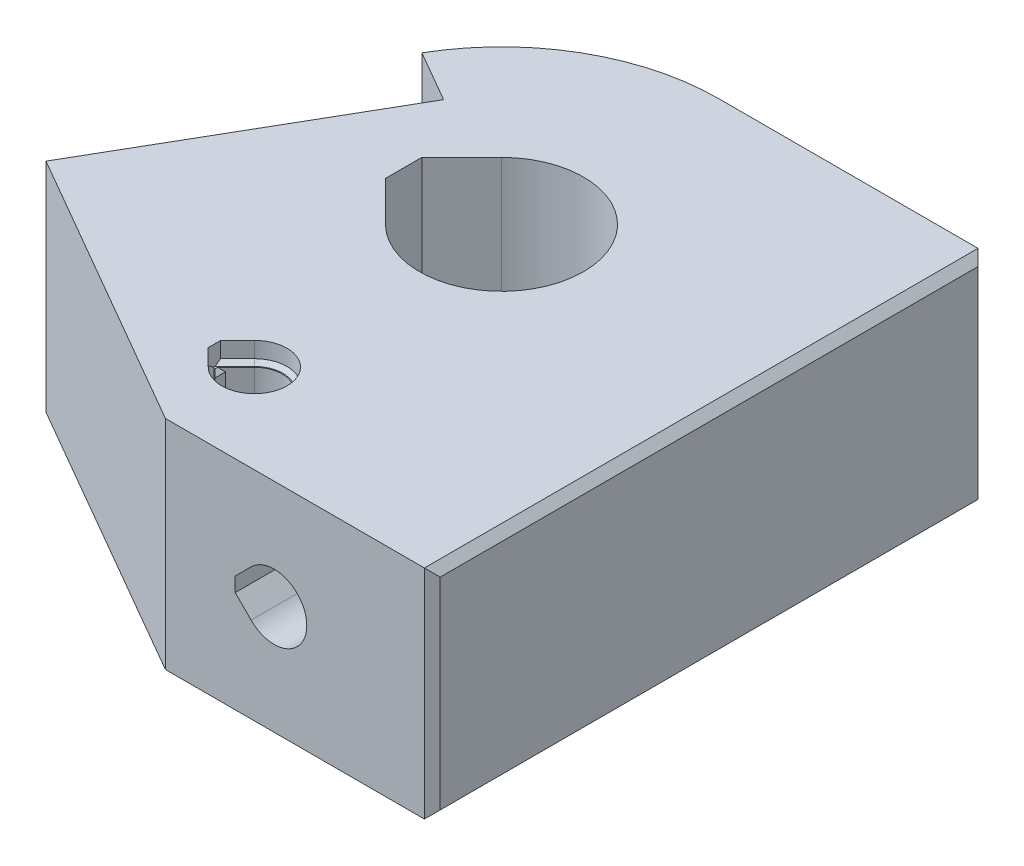
SolidWorks part; units mm, degrees
material "Custom Plastic"
ref_plane "Front Plane" through (0, 0, 0) normal (0, 0, 1) x (1, 0, 0)
ref_plane "Top Plane" through (0, 0, 0) normal (0, 1, 0) x (1, 0, 0)
ref_plane "Right Plane" through (0, 0, 0) normal (1, 0, 0) x (0, 0, -1)
sketch "Sketch1" plane through (0, 0, 0) normal (0, 1, 0) x (1, 0, 0)
  line L0 (-7.5, -1) -> (-21, -1)
  line L1 (-35.2894, 7.25) -> (-40.4856, 10.25) construction
  line L2 (-21, 24) -> (-6, 24) construction
  line L3 (0, 24) -> (0, 0) construction
  line L4 (-40.4856, 10.25) -> (-37.1244, 16.0718) construction
  line L5 (-22.7129, 20.1561) -> (-19.2871, 20.1561) construction
  line L6 (-21, 27) -> (-7.5, 27)
  line L7 (-7.5, -1) -> (-7.5, 27)
  line L8 (-35.2894, 7.25) -> (-21, -1)
  line L9 (-37.1244, 16.0718) -> (-31.9282, 13.0718) construction
  line L10 (-7.5, 11.5) -> (7.5, 20.5) construction
  line L11 (-7.5, 20.5) -> (7.5, 11.5) construction
  line L12 (-19.2871, 20.1561) -> (-18.0655, 18.9345) construction
  line L13 (-18.0655, 18.9345) -> (-21, 16) construction
  line L14 (-21, 16) -> (-23.9345, 18.9345) construction
  line L15 (-23.9345, 18.9345) -> (-22.7129, 20.1561) construction
  line L16 (-27.9282, 20) -> (-31.9282, 13.0718)
  line L17 (-27.9282, 20) -> (-30.5263, 21.5)
  line L18 (-31.9282, 13.0718) -> (-35.2894, 7.25)
  arc A0 (-21, 24) -> (-27.5362, 11.3872) centre (-21, 16) ccw construction
  circle A1 centre (-21, 16) radius 4.15
  arc A2 (-21, 27) -> (-30.5263, 21.5) centre (-21, 16) ccw
  point P10 (0, 16)
  point P22 (-21, 20.1561)
  dimension "D4" = 8.3
  dimension "D5" = 8
  dimension "D9" = 3
  dimension "D2" = 42
  dimension "D3" = 25
  dimension "D6" = 9
  dimension "D7" = 15
  dimension "D8" = 16
  dimension "D10" = 30
  dimension "D11" = 42
  dimension "D12" = 6
  dimension "D13" = 8
extrude "Boss-Extrude1" add sketch "Sketch1" along normal blind 11
sketch "Sketch2" plane through (0, 0, 1) normal (0, 0, 1) x (1, 0, 0)
  line L0 (-22.5, 21) -> (0, 21) construction
  line L1 (-15.5, 36.5) -> (15.5, 36.5) construction
  line L2 (-15.5, 36.5) -> (-15.5, 5.5) construction
  line L3 (-15.5, 5.5) -> (15.5, 5.5) construction
  line L4 (15.5, 36.5) -> (15.5, 5.5) construction
  line L5 (-15.5, 36.5) -> (15.5, 5.5) construction
  line L6 (-15.5, 5.5) -> (15.5, 36.5) construction
  line L9 (-21, 0) -> (-7.5, 0) construction
  circle A0 centre (-15.5, 36.5) radius 1.65 construction
  circle A1 centre (15.5, 36.5) radius 1.65 construction
  circle A2 centre (15.5, 5.5) radius 1.65 construction
  circle A4 centre (0, 21) radius 11.2 construction
  circle A5 centre (-15.5, 5.5) radius 1.65
  point P0 (0, 21)
  dimension "D2" = 3.3
  dimension "D3" = 22.4
  dimension "D1" = 31
  dimension "D4" = 21
extrude "Cut-Extrude1" cut sketch "Sketch2" against normal through all
sketch "Sketch3" plane through (0, 0, -27) normal (0, 0, -1) x (-1, 0, 0)
  circle A1 centre (15.5, 5.5) radius 3.7
  circle A2 centre (15.5, 5.5) radius 1.65 construction
  dimension "D1" = 7.4
extrude "Cut-Extrude2" cut sketch "Sketch3" against normal blind 11
sketch "Sketch5" plane through (0, 11, 0) normal (0, 1, 0) x (1, 0, 0)
  line L0 (0, 0) -> (0, 3.5) construction
  line L1 (-21, 3.5) -> (21, 3.5) construction
  line L3 (-21, 3.5) -> (-20.3764, 4.7535) construction
  line L4 (-20.3764, 4.7535) -> (-23.4917, 6.3032) construction
  line L5 (-21, 3.5) -> (-22.5871, 4.2896) construction
  line L6 (-22.5871, 4.2896) -> (-18.5083, 6.3032) construction
  line L7 (-18.5083, 6.3032) -> (-23.4917, 6.3032) construction
  circle A0 centre (-21, 3.5) radius 1.4
  circle A1 centre (-21, 16) radius 4.15 construction
  point P10 (-21, 6.3032)
  dimension "D1" = 2.8
  dimension "D2" = 42
  dimension "D3" = 12.5
extrude "Cut-Extrude4" cut sketch "Sketch5" against normal through all
ref_axis "Axis1" [suppressed] through (0, 6, -27) along (0, 0, 1)
ref_plane "Plane1" [suppressed] through (0, 6, 0) normal (0, 1, 0) x (1, 0, 0)
ref_axis "Axis2" through (-21, 0, -3.5) along (0, 1, 0)
ref_plane "Plane2" through (0, 5.5, 0) normal (0, 1, 0) x (1, 0, 0)
sketch "Sketch11" plane through (-29.6064, 0, -17.0933) normal (-0.866, 0, -0.5) x (-0.5, 0, 0.866)
  line L0 (15.2842, 5.5) -> (-15.2842, 5.5) construction
  line L1 (-3.3564, 11) -> (-3.3564, 0) construction
  circle A0 centre (3.6436, 5.5) radius 1.4
  dimension "D2" = 2.8
  dimension "D1" = 7
extrude "Cut-Extrude10" cut sketch "Sketch11" against normal blind 14
sketch "Sketch10" [suppressed] plane through (-29.6064, 0, -17.0933) normal (-0.866, 0, -0.5) x (-0.5, 0, 0.866)
  line L0 (0.8936, 11) -> (6.3936, 11)
  line L1 (3.6436, 2.1246) -> (6.3936, 3.7123)
  line L2 (6.3936, 3.7123) -> (6.3936, 11)
  line L3 (6.9561, 6.563) -> (3.6436, 8.4754) construction
  line L4 (3.6436, 8.4754) -> (1.4561, 7.2125) construction
  line L5 (0.8936, 11) -> (0.8936, 3.7123)
  line L6 (0.8936, 3.7123) -> (3.6436, 2.1246)
  line L7 (-3.3564, 11) -> (11.366, 11) construction
  circle A0 centre (3.6436, 5.3) radius 2.75 construction
  point P1 (3.6436, 5.5)
  dimension "D2" = 5.5
  dimension "D1" = 0.2
extrude "Cut-Extrude9" [suppressed] cut sketch "Sketch10" against normal blind 4 from offset 9 offset against normal yes
sketch "Sketch13" plane through (0, 0, -27) normal (0, 0, -1) x (-1, 0, 0)
  line L0 (15.5, 5.5) -> (18.1163, 8.1163)
  line L1 (18.1163, 8.1163) -> (19.94, 6.2926)
  line L2 (19.94, 6.2926) -> (19.94, 4.7074)
  line L3 (19.94, 4.7074) -> (18.1163, 2.8837)
  line L4 (18.1163, 2.8837) -> (15.5, 5.5)
  line L5 (15.2842, 5.5) -> (-15.2842, 5.5) construction
  circle A0 centre (15.5, 5.5) radius 3.7 construction
  arc A2 (16.85, 2.0551) -> (16.85, 8.9449) centre (15.5, 5.5) ccw construction
  point P7 (19.94, 5.5)
  point P9 (19.2, 5.5)
  dimension "D1" = 0.74
extrude "Cut-Extrude12" [suppressed] cut sketch "Sketch13" against normal up to surface (11 mm away)
sketch "Sketch14" plane through (0, 0, 1) normal (0, 0, 1) x (1, 0, 0)
  line L0 (-15.5, 5.5) -> (-16.6667, 6.6667)
  line L1 (-16.6667, 6.6667) -> (-17.47, 5.8635)
  line L2 (-17.47, 5.8635) -> (-17.47, 5.1365)
  line L3 (-17.47, 5.1365) -> (-16.6667, 4.3333)
  line L4 (-16.6667, 4.3333) -> (-15.5, 5.5)
  line L5 (15.2842, 5.5) -> (-15.2842, 5.5) construction
  circle A0 centre (-15.5, 5.5) radius 1.65 construction
  point P9 (-17.15, 5.5)
  dimension "D1" = 0.32
extrude "Cut-Extrude13" [suppressed] cut sketch "Sketch14" against normal through all
sketch "Sketch16" plane through (0, 0, 0) normal (0, -1, 0) x (1, 0, 0)
  line L0 (-21, -16) -> (-23.9345, -18.9345)
  line L1 (-23.9345, -18.9345) -> (-25.95, -16.919)
  line L2 (-25.95, -16.919) -> (-25.95, -15.081)
  line L3 (-25.95, -15.081) -> (-23.9345, -13.0655)
  line L4 (-23.9345, -13.0655) -> (-21, -16)
  circle A0 centre (-21, -16) radius 4.15 construction
  point P7 (-25.15, -16)
  dimension "D1" = 0.8
extrude "Cut-Extrude14" cut sketch "Sketch16" against normal through all
chamfer "Chamfer1" [suppressed] distance 0.4 angle 45
sketch "Sketch17" plane through (0, 0, -27) normal (0, 0, -1) x (-1, 0, 0)
  line L0 (15.5, 5.5) -> (18.1163, 2.8837)
  line L1 (18.1163, 2.8837) -> (19.94, 4.7074)
  line L2 (19.94, 4.7074) -> (19.94, 6.2926)
  line L3 (19.94, 6.2926) -> (18.1163, 8.1163)
  line L4 (18.1163, 8.1163) -> (15.5, 5.5)
  line L5 (15.5, 5.5) -> (19.94, 5.5) construction
  arc A0 (16.85, 8.9449) -> (16.85, 2.0551) centre (15.5, 5.5) ccw construction
  circle A1 centre (15.5, 5.5) radius 3.7 construction
  arc A2 (16.85, 2.0551) -> (16.85, 8.9449) centre (15.5, 5.5) ccw construction
  point P6 (19.2, 5.5)
  dimension "D1" = 0.74
extrude "Cut-Extrude15" cut sketch "Sketch17" against normal up to surface (11 mm away) up to face at (-14.8375, 5.5, -16)
sketch "Sketch18" plane through (0, 0, 1) normal (0, 0, 1) x (1, 0, 0)
  line L0 (-15.5, 5.5) -> (-16.6667, 6.6667)
  line L1 (-16.6667, 6.6667) -> (-17.47, 5.8635)
  line L2 (-17.47, 5.8635) -> (-17.47, 5.1365)
  line L3 (-17.47, 5.1365) -> (-16.6667, 4.3333)
  line L4 (-16.6667, 4.3333) -> (-15.5, 5.5)
  line L5 (-15.5, 5.5) -> (-17.47, 5.5) construction
  circle A0 centre (-15.5, 5.5) radius 1.65 construction
  point P9 (-17.15, 5.5)
  dimension "D1" = 0.32
extrude "Cut-Extrude16" cut sketch "Sketch18" against normal through all
sketch "Sketch19" [suppressed] plane through (-29.6064, 0, -17.0933) normal (-0.866, 0, -0.5) x (-0.5, 0, 0.866)
  line L0 (3.6436, 5.5) -> (4.6335, 6.4899)
  line L1 (4.6335, 6.4899) -> (4.0694, 7.0541)
  line L2 (4.0694, 7.0541) -> (3.2178, 7.0541)
  line L3 (3.2178, 7.0541) -> (2.6536, 6.4899)
  line L4 (2.6536, 6.4899) -> (3.6436, 5.5)
  circle A0 centre (3.6436, 5.5) radius 1.4 construction
  circle A1 centre (3.6436, 5.5) radius 1.4 construction
  point P6 (4.3047, 6.7341)
  dimension "D1" = 0.32
extrude "Cut-Extrude17" [suppressed] cut sketch "Sketch19" against normal up to surface (14 mm away)
sketch "Sketch23" plane through (0, 0, 0) normal (0, -1, 0) x (1, 0, 0)
  line L0 (-21.9899, -2.5101) -> (-22.72, -3.2401)
  line L1 (-22.72, -3.2401) -> (-22.72, -3.7599)
  line L2 (-22.72, -3.7599) -> (-21.9899, -4.4899)
  line L3 (-21.9899, -4.4899) -> (-21.9899, -2.5101)
  line L4 (-21, -3.5) -> (-22.72, -3.5) construction
  circle A0 centre (-21, -3.5) radius 1.4 construction
  point P9 (-22.4, -3.5)
  dimension "D1" = 0.32
extrude "Cut-Extrude21" cut sketch "Sketch23" against normal through all
sketch "Sketch20" plane through (0, 11, 0) normal (0, 1, 0) x (1, 0, 0)
  circle A0 centre (-21, 3.5) radius 1.65
  dimension "D1" = 3.3
extrude "Cut-Extrude18" cut sketch "Sketch20" against normal blind 1
sketch "Sketch21" plane through (0, 0, 0) normal (0, -1, 0) x (1, 0, 0)
  circle A0 centre (-21, -3.5) radius 1.65
  circle A1 centre (-21, -3.5) radius 1.65 construction
extrude "Cut-Extrude19" cut sketch "Sketch21" against normal blind 1
sketch "Sketch24" plane through (0, 0, 0) normal (0, -1, 0) x (1, 0, 0)
  line L0 (-22.1667, -2.3333) -> (-23.02, -3.1865)
  line L1 (-23.02, -3.1865) -> (-23.02, -3.8135)
  line L2 (-23.02, -3.8135) -> (-22.1667, -4.6667)
  line L3 (-22.1667, -4.6667) -> (-22.1667, -2.3333)
  line L4 (-22.6074, -3.1275) -> (-21.9899, -2.5101) construction
  line L5 (-22.72, -3.2401) -> (-22.72, -3.7599) construction
  arc A0 (-22.6074, -3.8725) -> (-22.6074, -3.1275) centre (-21, -3.5) ccw construction
  dimension "D1" = 0.3
extrude "Cut-Extrude22" cut sketch "Sketch24" against normal up to surface (1 mm away) up to face at (-20.8868, 1, -3.5)
sketch "Sketch25" plane through (0, 11, 0) normal (0, 1, 0) x (1, 0, 0)
  line L0 (-23.02, 3.1865) -> (-23.02, 3.8135)
  line L1 (-23.02, 3.8135) -> (-22.1667, 4.6667)
  line L2 (-22.1667, 4.6667) -> (-22.1667, 2.3333)
  line L3 (-22.1667, 2.3333) -> (-23.02, 3.1865)
  arc A0 (-22.6074, 3.1275) -> (-22.6074, 3.8725) centre (-21, 3.5) ccw construction
extrude "Cut-Extrude23" cut sketch "Sketch25" against normal up to surface (1 mm away) up to face at (-20.8868, 10, -3.5)
fillet "Fillet1" [suppressed] radius 3
chamfer "Chamfer4" distance 0.4 angle 45 4 edges at (-7.5, 5.5, 1) (-7.5, 11, -13) (-7.5, 5.5, -27) (-7.5, 0, -13)
sketch "Sketch22" plane through (-29.6064, 0, -17.0933) normal (-0.866, 0, -0.5) x (-0.5, 0, 0.866)
  line L0 (2.4415, 6.7021) -> (3.2694, 7.53) construction
  line L1 (3.2694, 7.53) -> (4.0178, 7.53) construction
  line L2 (4.0178, 7.53) -> (4.8457, 6.7021) construction
  arc A0 (2.4415, 6.7021) -> (4.8457, 6.7021) centre (3.6436, 5.5) ccw
  circle A1 centre (3.6436, 5.5) radius 1.4 construction
  arc A2 (4.8457, 6.7021) -> (2.4415, 6.7021) centre (3.6436, 5.5) ccw
  point P1 (3.6436, 7.2)
  dimension "D1" = 1.7
  dimension "D2" = 0.33
extrude "Cut-Extrude20" cut sketch "Sketch22" against normal blind 9
chamfer "Chamfer3" [suppressed] distance 0.6 angle 15
chamfer "Chamfer2" [suppressed] distance 0.4 angle 45
chamfer "Chamfer5" distance 0.2 angle 45 8 edges at (-22.355, 1, -4.1249) (-19.6, 1, -3.5) (-22.355, 1, -2.8751) (-22.72, 1, -3.5) (-22.72, 10, -3.5) (-22.5934, 10, -2.7599) (-22.5934, 10, -4.2401) (-19.35, 10, -3.5)
sketch "Sketch26" plane through (-5.683, 0, 9.8433) normal (-0.5, 0, 0.866) x (0.866, 0, 0.5)
  line L0 (-34.1865, 0) -> (-34.1865, 2)
  line L2 (-34.1865, 2) -> (-37.6865, 2)
  line L3 (-34.1865, 11) -> (-34.1865, 0) construction
  line L4 (-37.6865, 2) -> (-37.6865, 0)
  line L5 (-37.6865, 0) -> (-34.1865, 0)
  line L6 (-34.1865, 0) -> (-17.6865, 0) construction
  line L7 (-37.6865, 11) -> (-34.1865, 11)
  line L8 (-37.6865, 11) -> (-37.6865, 9)
  line L9 (-37.6865, 9) -> (-34.1865, 9)
  line L10 (-34.1865, 11) -> (-34.1865, 9)
  dimension "D1" = 2
  dimension "D2" = 3.5
extrude "Cut-Extrude24" [suppressed] cut sketch "Sketch26" against normal up to next
chamfer "Chamfer6" [suppressed] distance 3 angle 10
chamfer "Chamfer7" [suppressed] distance 2 angle 45
chamfer "Chamfer9" [suppressed] distance 1 angle 8
sketch "Sketch27" [suppressed] plane through (0, 5.5, 0) normal (0, 1, 0) x (1, 0, 0)
  line L0 (-38.5803, 9.15) -> (-38.5803, 13.55)
  line L1 (-38.1244, 14.3397) -> (-39.4856, 11.9821) construction
  line L2 (-38.5803, 13.55) -> (-40.4856, 10.25)
  line L3 (-40.4856, 10.25) -> (-38.5803, 9.15)
  line L4 (-21, -1) -> (-35.2894, 7.25) construction
  line L5 (-37.8205, 9.866) -> (-38.3205, 9) construction
  dimension "D1" = 0.3
extrude "Cut-Extrude25" [suppressed] cut sketch "Sketch27" against normal through all and the other way through all
fillet "Fillet2" [suppressed] radius 1
